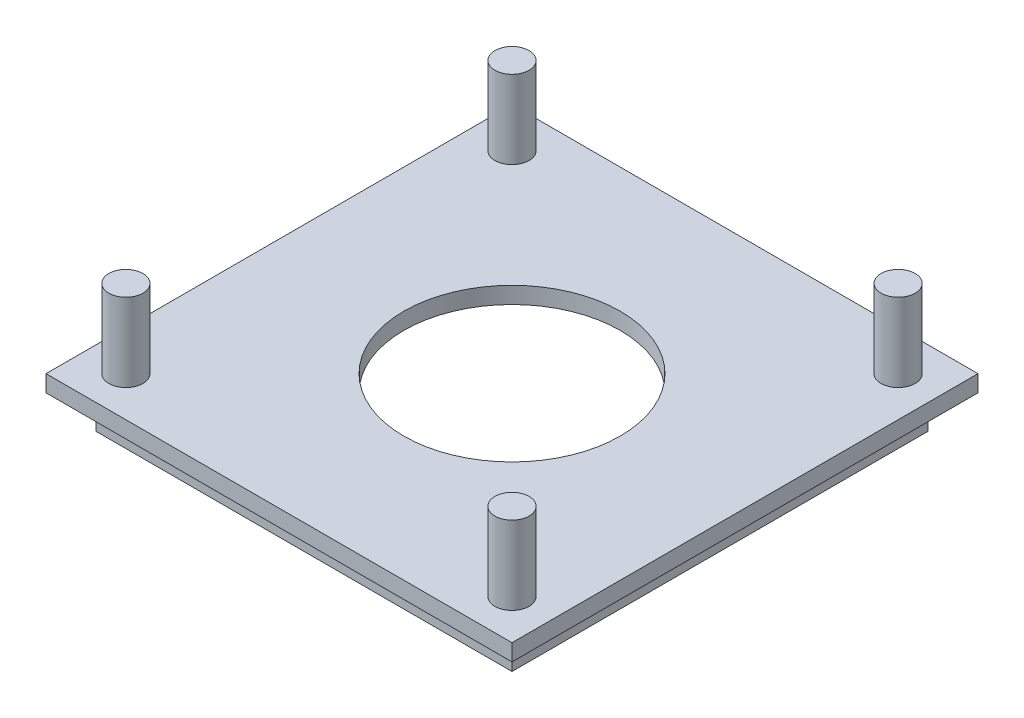
SolidWorks part; units mm, degrees
ref_plane "Front Plane" through (0, 0, 0) normal (0, 0, 1) x (1, 0, 0)
ref_plane "Top Plane" through (0, 0, 0) normal (0, 1, 0) x (1, 0, 0)
ref_plane "Right Plane" through (0, 0, 0) normal (1, 0, 0) x (0, 0, -1)
sketch "Sketch1" plane through (0, 0, 0) normal (0, 1, 0) x (1, 0, 0)
  line L1 (-70, -70) -> (70, -70)
  line L2 (-70, -70) -> (-70, 70)
  line L3 (-70, 70) -> (70, 70)
  line L4 (70, -70) -> (70, 70)
  line L5 (-70, -70) -> (70, 70) construction
  line L6 (-70, 70) -> (70, -70) construction
  point P0 (0, 0)
  dimension "D1" = 140
  dimension "D2" = 140
extrude "Boss-Extrude1" add sketch "Sketch1" along normal blind 5
sketch "Sketch3" plane through (0, 5, 0) normal (0, 1, 0) x (1, 0, 0)
  circle A0 centre (0, 0) radius 32.5
  dimension "D1" = 65
extrude "Cut-Extrude1" cut sketch "Sketch3" against normal up to next
sketch "Sketch4" plane through (0, 5, 0) normal (0, 1, 0) x (1, 0, 0)
  line L0 (-58, 58) -> (58, 58) construction
  line L1 (0, 0) -> (0, 72.9846) construction
  line L2 (0, -2.75) -> (0, 2.75) construction
  line L3 (63, 63) -> (53, 63) construction
  line L4 (-63, 53) -> (-53, 53) construction
  line L5 (-63, 53) -> (-63, 63) construction
  line L6 (-63, 63) -> (-53, 63) construction
  line L7 (-53, 53) -> (-53, 63) construction
  line L8 (-63, 53) -> (-53, 63) construction
  line L9 (-63, 63) -> (-53, 53) construction
  line L10 (53, 53) -> (53, 63) construction
  line L11 (63, 53) -> (53, 53) construction
  line L12 (63, 53) -> (63, 63) construction
  line L13 (-2.75, 0) -> (2.75, 0) construction
  line L14 (63, -53) -> (63, -63) construction
  line L15 (63, -53) -> (53, -53) construction
  line L16 (53, -53) -> (53, -63) construction
  line L17 (63, -63) -> (53, -63) construction
  line L18 (-63, -63) -> (-53, -63) construction
  line L19 (-53, -53) -> (-53, -63) construction
  line L20 (-63, -53) -> (-53, -53) construction
  line L21 (-63, -53) -> (-63, -63) construction
  circle A0 centre (-58, 58) radius 5.125
  circle A1 centre (58, 58) radius 5.125
  circle A2 centre (58, -58) radius 5.125
  circle A3 centre (-58, -58) radius 5.125
  point P6 (0, 58)
  point P26 (-63, -58)
  dimension "D2" = 10
  dimension "D4" = 10.25
  dimension "D1" = 116
  dimension "D3" = 116
extrude "Boss-Extrude2" add sketch "Sketch4" along normal blind 23.5
sketch "Sketch5" plane through (0, 0, 0) normal (0, -1, 0) x (1, 0, 0)
  line L1 (-62.5, -62.5) -> (62.5, -62.5)
  line L2 (-62.5, -62.5) -> (-62.5, 62.5)
  line L3 (-62.5, 62.5) -> (62.5, 62.5)
  line L4 (62.5, -62.5) -> (62.5, 62.5)
  line L5 (-62.5, -62.5) -> (62.5, 62.5) construction
  line L6 (-62.5, 62.5) -> (62.5, -62.5) construction
  line L11 (-55.5, -55.5) -> (55.5, 55.5) construction
  line L12 (-55.5, 55.5) -> (55.5, -55.5) construction
  line L13 (-60.5, -60.5) -> (60.5, -60.5)
  line L14 (-60.5, -60.5) -> (-60.5, 60.5)
  line L15 (-60.5, 60.5) -> (60.5, 60.5)
  line L16 (60.5, -60.5) -> (60.5, 60.5)
  line L17 (-60.5, -60.5) -> (60.5, 60.5) construction
  line L18 (-60.5, 60.5) -> (60.5, -60.5) construction
  line L23 (-57.5, -57.5) -> (57.5, 57.5) construction
  line L24 (-57.5, 57.5) -> (57.5, -57.5) construction
  point P0 (0, 0)
  point P6 (0, 0)
  point P11 (0, 0)
  point P16 (0, 0)
  dimension "D1" = 125
  dimension "D2" = 2
extrude "Boss-Extrude3" add sketch "Sketch5" along normal blind 10 contours L1 L4 L3 L2 L16 L13 L14 L15 region at (-60.7322, 0, 0)
